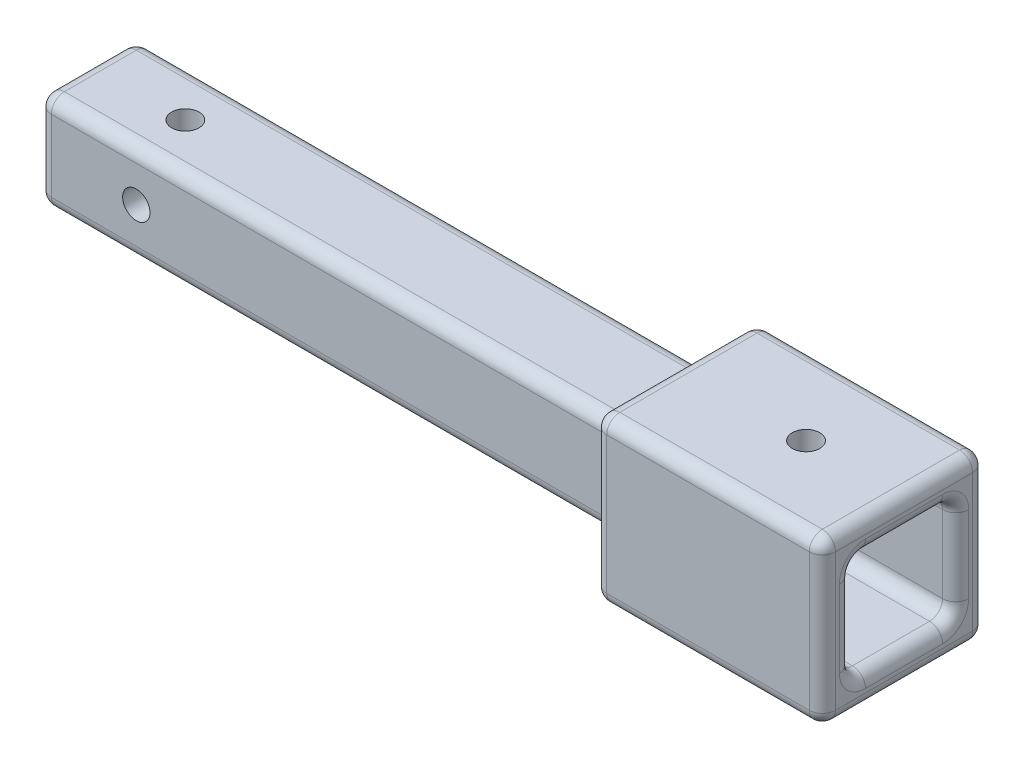
SolidWorks part; units mm, degrees
ref_plane "Front Plane" through (0, 0, 0) normal (0, 0, 1) x (1, 0, 0)
ref_plane "Top Plane" through (0, 0, 0) normal (0, 1, 0) x (1, 0, 0)
ref_plane "Right Plane" through (0, 0, 0) normal (1, 0, 0) x (0, 0, -1)
sketch "Sketch1" plane through (0, 0, 0) normal (0, 1, 0) x (1, 0, 0)
  line L0 (90, -15) -> (90, -20)
  line L1 (0, 0) -> (90, 0)
  line L2 (0, 0) -> (0, -15)
  line L3 (0, -15) -> (90, -15)
  line L4 (90, 0) -> (90, -15)
  line L5 (90, 5) -> (125, 5)
  line L6 (90, 5) -> (90, 0)
  line L7 (90, -20) -> (125, -20)
  line L8 (125, 5) -> (125, -20)
  line L9 (90, -15) -> (90, 0)
  dimension "D1" = 90
  dimension "D2" = 15
  dimension "D3" = 35
  dimension "D4" = 25
  dimension "D5" = 5
extrude "Boss-Extrude1" add sketch "Sketch1" along normal blind 7.5 and the other way blind 7.5 contours L4 L1 L2 L3 region at (45, 0, 7.5)
extrude "Boss-Extrude2" add sketch "Sketch1<3>" along normal blind 12.5 and the other way blind 12.5 contours L8 L5 L6 L4 L0 L7 region at (107.5, 0, 7.5)
sketch "Sketch1<3>" plane through (0, 0, 0) normal (0, 1, 0) x (1, 0, 0) same geometry as "Sketch1"
sketch "Sketch3" plane through (0, 0, 15) normal (0, 0, 1) x (1, 0, 0)
  line L0 (0, -7.5) -> (0, 7.5) construction
  line L1 (0, 7.5) -> (90, 7.5) construction
  circle A0 centre (15, 0) radius 2.1
  dimension "D1" = 15
  dimension "D3" = 4.2
  dimension "D2" = 7.5
extrude "Cut-Extrude1" cut sketch "Sketch3" against normal through all
sketch "Sketch5" plane through (0, 12.5, 0) normal (0, 1, 0) x (1, 0, 0)
  line L0 (90, -20) -> (125, -20) construction
  line L1 (125, 5) -> (125, -20) construction
  circle A0 centre (110, -7.5) radius 2.1
  dimension "D1" = 12.5
  dimension "D3" = 4.2
  dimension "D2" = 15
extrude "Cut-Extrude3" cut sketch "Sketch5" against normal through all
sketch "Sketch6" plane through (125, 0, 0) normal (1, 0, 0) x (0, 0, -1)
  line L0 (-20, -12.5) -> (-20, 12.5) construction
  line L1 (-15.4, 7.9) -> (0.4, 7.9)
  line L2 (-15.4, 7.9) -> (-15.4, -7.9)
  line L3 (-15.4, -7.9) -> (0.4, -7.9)
  line L4 (0.4, 7.9) -> (0.4, -7.9)
  line L7 (5, 12.5) -> (-20, 12.5) construction
  dimension "D1" = 15.8
  dimension "D2" = 15.8
  dimension "D3" = 4.6
  dimension "D4" = 4.6
extrude "Cut-Extrude4" cut sketch "Sketch6" against normal blind 32
sketch "Sketch8" plane through (0, -7.5, 0) normal (0, -1, 0) x (1, 0, 0)
  line L0 (0, 0) -> (0, 15) construction
  line L1 (0, 15) -> (90, 15) construction
  circle A0 centre (15, 7.5) radius 2.1
  point P2 (0, 7.5)
  dimension "D1" = 4.2
  dimension "D2" = 15
  dimension "D3" = 7.5
extrude "Cut-Extrude5" cut sketch "Sketch8" against normal through all
fillet "Fillet1" radius 2 36 edges at (125, -12.5, 7.5) (125, 0, 20) (125, 12.5, 7.5) (125, 0, -5) (93, -7.9, 7.5) (109, 7.9, 15.4) (93, 7.9, 7.5) (93, 0, -0.4) (93, 0, 15.4) (109, -7.9, 15.4) (109, -7.9, -0.4) (109, 7.9, -0.4) (107.5, 12.5, -5) (90, 12.5, 7.5) (107.5, 12.5, 20) (107.5, -12.5, 20) (90, -12.5, 7.5) (107.5, -12.5, -5) (90, 0, -5) (90, 0, 0) (90, -7.5, 7.5) (90, 0, 15) (90, 7.5, 7.5) (0, 0, 0) (0, 0, 15) (0, -7.5, 7.5) (0, 7.5, 7.5) (45, -7.5, 0) (45, -7.5, 15) (45, 7.5, 15) (45, 7.5, 0) (125, -7.9, 7.5) (125, 0, 15.4) (125, 7.9, 7.5) (125, 0, -0.4) (90, 0, 20)
